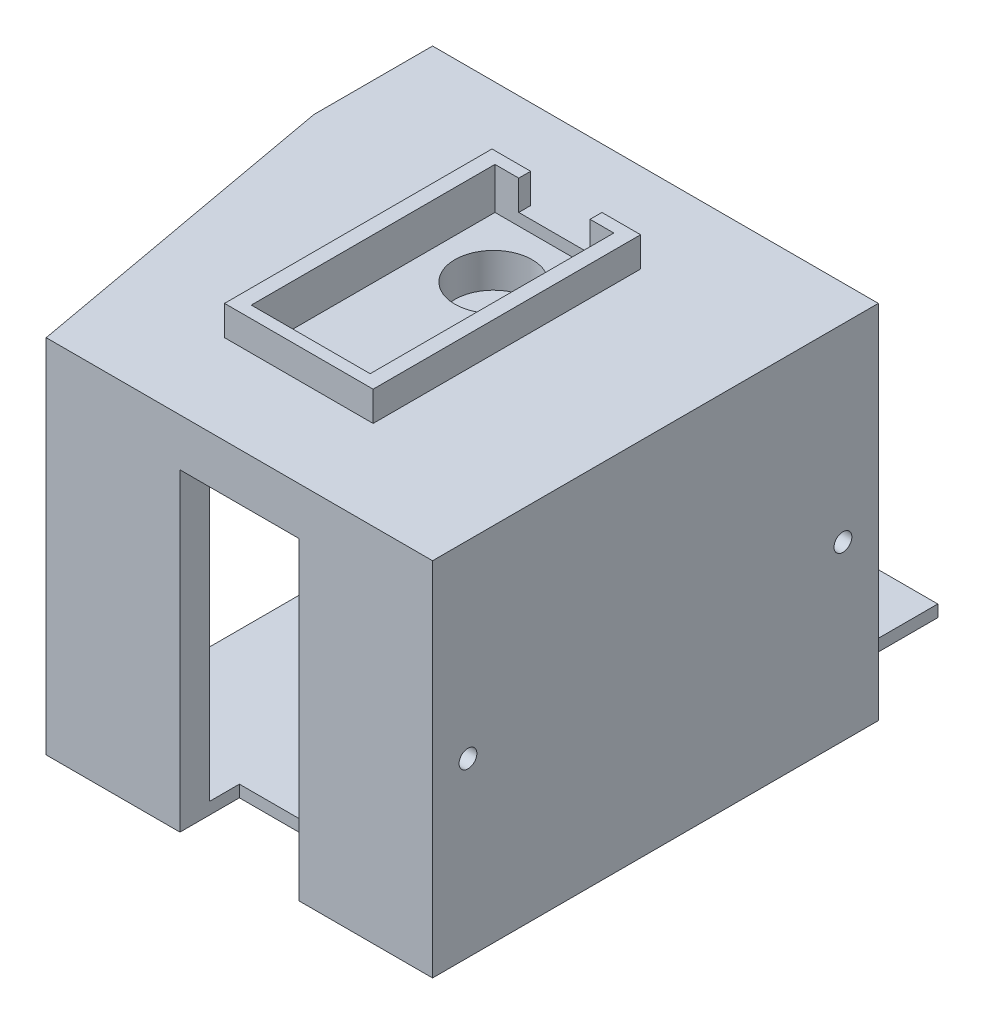
SolidWorks part; units mm, degrees
ref_plane "Front Plane" through (0, 0, 0) normal (0, 0, 1) x (1, 0, 0)
ref_plane "Top Plane" through (0, 0, 0) normal (0, 1, 0) x (1, 0, 0)
ref_plane "Right Plane" through (0, 0, 0) normal (1, 0, 0) x (0, 0, -1)
sketch "Sketch1" plane through (0, 0, 0) normal (0, 1, 0) x (1, 0, 0)
  line L1 (0, 0) -> (55, 0)
  line L2 (0, 0) -> (0, 65)
  line L3 (0, 65) -> (55, 65)
  line L4 (55, 0) -> (55, 65)
  dimension "D1" = 55
  dimension "D2" = 65
extrude "Base" add sketch "Sketch1" along normal blind 2
sketch "Sketch2" plane through (0, 2, 0) normal (0, 1, 0) x (1, 0, 0)
  line L0 (0, 0) -> (55, 0) construction
  line L2 (55, 65) -> (0, 65) construction
  circle A0 centre (3, 3.5) radius 1.125
  circle A1 centre (52, 3.5) radius 1.125
  circle A2 centre (3, 61.5) radius 1.125
  circle A3 centre (52, 61.5) radius 1.125
  point P12 (27.5, 0)
  dimension "D1" = 2.25
  dimension "D2" = 24.5
  dimension "D3" = 24.5
  dimension "D4" = 58
  dimension "D5" = 3.5
extrude "PiMountScrewHoles" cut sketch "Sketch2" against normal up to surface (2 mm away) up to face at (27.5, 0, -32.5)
sketch "Sketch3" plane through (0, 0, 0) normal (-1, 0, 0) x (0, 0, 1)
  line L0 (-65, 0) -> (0, 0) construction
  line L1 (-65, 2) -> (-45, 2)
  line L2 (-65, 2) -> (-65, 0)
  line L3 (-65, 0) -> (-45, 0)
  line L4 (-45, 2) -> (-45, 0)
  dimension "D1" = 20
extrude "PlateLegExt-1" add sketch "Sketch3" along normal blind 10
sketch "Sketch19" plane through (0, 0, -65) normal (0, 0, -1) x (-1, 0, 0)
  line L1 (-55, 2) -> (0, 2)
  line L2 (-55, 2) -> (-55, 0)
  line L3 (-55, 0) -> (0, 0)
  line L4 (0, 2) -> (0, 0)
extrude "PiFrontBase" add sketch "Sketch19" along normal blind 20
sketch "Sketch21" plane through (55, 0, 0) normal (1, 0, 0) x (0, 0, -1)
  line L0 (0, 0) -> (85, 0) construction
  line L1 (0, 2) -> (65, 2)
  line L2 (0, 2) -> (0, 0)
  line L3 (0, 0) -> (65, 0)
  line L4 (65, 2) -> (65, 0)
  point P7 (0, 0)
extrude "BatteryWall-Ext" add sketch "Sketch21" along normal blind 10
sketch "Sketch22" plane through (0, 0, 0) normal (0, 0, 1) x (1, 0, 0)
  line L0 (0, 0) -> (65, 0) construction
  line L1 (0, 2) -> (22.5, 2)
  line L2 (0, 2) -> (0, 0)
  line L3 (0, 0) -> (22.5, 0)
  line L4 (22.5, 2) -> (22.5, 0)
  line L6 (42.5, 2) -> (55, 2)
  line L7 (42.5, 2) -> (42.5, 0)
  line L8 (42.5, 0) -> (55, 0)
  line L11 (0, 2) -> (65, 2) construction
  line L12 (55, 2) -> (55, 0)
  line L13 (55, 0) -> (55, 2) construction
  point P16 (32.5, 0)
  dimension "D1" = 10
  dimension "D2" = 20
extrude "PlateLegExt-2" add sketch "Sketch22" along normal blind 10
sketch "Sketch30" plane through (55, 0, 0) normal (1, 0, 0) x (0, 0, -1)
  line L1 (-10, 2) -> (0, 2)
  line L2 (-10, 2) -> (-10, 0)
  line L3 (-10, 0) -> (0, 0)
  line L4 (0, 2) -> (0, 0)
extrude "CornerExtension" add sketch "Sketch30" along normal up to vertex (10 mm away) up to point (65, 2, 0)
sketch "Sketch23" plane through (0, 2, 0) normal (0, 1, 0) x (1, 0, 0)
  line L0 (65, 65) -> (55, 65) construction
  line L2 (22.5, -5) -> (0, -5)
  line L3 (22.5, -5) -> (22.5, -10)
  line L4 (-5, 65) -> (-10, 65)
  line L8 (60, 65) -> (65, 65)
  line L9 (60, 65) -> (60, -5)
  line L11 (65, 65) -> (65, -10)
  line L14 (-5, 65) -> (-5, 45)
  line L15 (-5, 45) -> (-10, 45)
  line L16 (-10, 65) -> (-10, 45)
  line L21 (22.5, -10) -> (0, -10)
  line L22 (0, -5) -> (0, -10)
  line L23 (22.5, -10) -> (22.5, 0) construction
  line L24 (0, 65) -> (-10, 65) construction
  line L25 (42.5, -10) -> (42.5, 0) construction
  line L26 (42.5, -10) -> (65, -10)
  line L27 (42.5, -10) -> (42.5, -5)
  line L30 (65, 65) -> (65, -10) construction
  line L31 (65, -10) -> (42.5, -10) construction
  line L32 (42.5, -5) -> (60, -5)
extrude "PlateLegs" add sketch "Sketch23" along normal blind 50.8
sketch "Sketch29" plane through (65, 0, 0) normal (1, 0, 0) x (0, 0, -1)
  line L0 (-10, 0) -> (65, 0) construction
  circle A0 centre (59.045, 29) radius 1.5
  circle A1 centre (-4.043, 29) radius 1.5
  point P4 (4.5653, 27.1468)
  point P5 (-3.3548, 27.3357)
  point P8 (27.5, 0)
  point P9 (0, 0)
  dimension "D1" = 3
  dimension "D2" = 63.088
  dimension "D3" = 31.545
  dimension "D4" = 29
extrude "Battery-ScrewHoles" cut sketch "Sketch29" against normal up to surface (5 mm away) up to face at (60, 27.4, -30)
sketch "Sketch24" plane through (0, 52.8, 0) normal (0, 1, 0) x (1, 0, 0)
  line L7 (0, -10) -> (65, -10)
  line L8 (42.5, -10) -> (65, -10) construction
  line L9 (65, -10) -> (65, 65)
  line L10 (65, 65) -> (-10, 65)
  line L11 (-10, 65) -> (-10, 45)
  line L12 (-10, 45) -> (0, -10)
extrude "RotatorPlate" add sketch "Sketch24" along normal blind 8
sketch "Sketch25" plane through (0, 60.8, 0) normal (0, 1, 0) x (1, 0, 0)
  line L2 (37.5, 7) -> (37.5, 48)
  line L4 (17.5, 7) -> (17.5, 48)
  line L7 (37.5, 48) -> (17.5, 48)
  line L8 (17.5, 7) -> (37.5, 7)
  line L9 (65, -10) -> (65, 65) construction
  line L11 (65, 65) -> (-10, 65) construction
  point P8 (27.5, 65)
  point P9 (65, 27.5)
  point P10 (37.5, 27.5)
  point P11 (27.5, 48)
  dimension "D1" = 41
  dimension "D2" = 20
extrude "Inset-Servo" cut sketch "Sketch25" against normal blind 2
sketch "Sketch26" plane through (0, 58.8, 0) normal (0, 1, 0) x (1, 0, 0)
  line L3 (37.5, 48) -> (17.5, 48) construction
  circle A0 centre (27.5, 37.75) radius 1.5
  point P2 (0, 0)
  point P8 (27.5, 48)
  dimension "D1" = 3
  dimension "D2" = 10.25
extrude "Hole-ServoScrew" cut sketch "Sketch26" against normal up to surface (6 mm away) up to face at (20.9091, 52.8, -15.4545)
sketch "Sketch27" plane through (0, 58.8, 0) normal (0, 1, 0) x (1, 0, 0)
  circle A0 centre (27.5, 37.75) radius 6.5
  circle A1 centre (27.5, 37.75) radius 1.5 construction
  dimension "D1" = 13
extrude "Inset-ServoAxle" cut sketch "Sketch27" against normal blind 5.8
sketch "Sketch28" plane through (0, 60.8, 0) normal (0, 1, 0) x (1, 0, 0)
  line L0 (37.5, 48) -> (33.5, 48)
  line L1 (37.5, 7) -> (17.5, 7)
  line L2 (37.5, 7) -> (37.5, 48)
  line L4 (17.5, 7) -> (17.5, 48)
  line L5 (40, 5) -> (15, 5)
  line L6 (40, 5) -> (40, 50)
  line L8 (15, 5) -> (15, 50)
  line L9 (37.5, 48) -> (17.5, 48) construction
  line L10 (17.5, 48) -> (21.5, 48)
  line L11 (37.5, 7) -> (37.5, 48) construction
  line L12 (33.5, 48) -> (33.5, 50)
  line L13 (33.5, 50) -> (40, 50)
  line L14 (21.5, 48) -> (21.5, 50)
  line L15 (21.5, 50) -> (15, 50)
  line L16 (37.5, 48) -> (17.5, 48) construction
  line L17 (17.5, 7) -> (37.5, 7) construction
  line L18 (17.5, 48) -> (17.5, 7) construction
  point P10 (0, 0)
  point P15 (27.5, 7)
  point P19 (27.5, 5)
  point P20 (40, 27.5)
  point P21 (37.5, 27.5)
  point P22 (0, 0)
  point P25 (0, 0)
  point P26 (0, 0)
  point P28 (27.5, 48)
  point P29 (21.5, 49)
  dimension "D1" = 6
  dimension "D2" = 12
  dimension "D3" = 45
  dimension "D4" = 25
extrude "RetainingWalls-Servo" add sketch "Sketch28" along normal blind 5
equation "\"PlateLegExtent\"= 10mm"
equation "\"D1@PlateLegExt-1\" = \"PlateLegExtent\""
equation "\"PlateLegHeight\"= 2in"
equation "\"D1@BatteryWall-Ext\" = \"PlateLegExtent\""
equation "\"D1@PlateLegExt-2\" = \"PlateLegExtent\""
equation "\"D1@PlateLegs\" = \"PlateLegHeight\""
